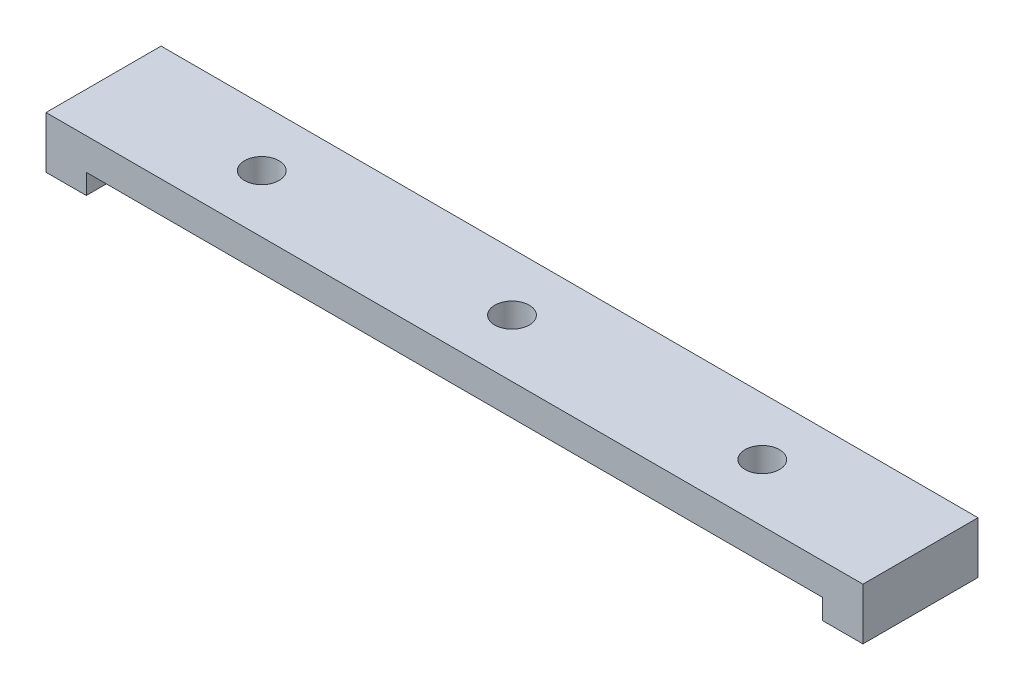
SolidWorks part; units mm, degrees
material "1060 Alloy"
ref_plane "Front Plane" through (0, 0, 0) normal (0, 0, 1) x (1, 0, 0)
ref_plane "Top Plane" through (0, 0, 0) normal (0, 1, 0) x (1, 0, 0)
ref_plane "Right Plane" through (0, 0, 0) normal (1, 0, 0) x (0, 0, -1)
sketch "Sketch1" plane through (0, 0, 0) normal (0, 1, 0) x (1, 0, 0)
  line L1 (0, 0) -> (71, 0)
  line L2 (0, 0) -> (0, 10)
  line L3 (0, 10) -> (71, 10)
  line L4 (71, 0) -> (71, 10)
  circle A0 centre (13.75, 5) radius 1.5
  circle A1 centre (35.5, 5) radius 1.5
  circle A2 centre (57.25, 5) radius 1.5
  dimension "D3" = 3
  dimension "D4" = 5
  dimension "D5" = 21.75
  dimension "D1" = 10
  dimension "D2" = 71
  dimension "D6" = 21.75
  dimension "D7" = 35.5
extrude "Boss-Extrude1" add sketch "Sketch1" along normal blind 4.5
sketch "Sketch2" plane through (0, 0, 0) normal (0, -1, 0) x (1, 0, 0)
  line L0 (0, 0) -> (71, 0) construction
  line L1 (3.5, 0) -> (67.5, 0)
  line L2 (3.5, 0) -> (3.5, -10)
  line L3 (3.5, -10) -> (67.5, -10)
  line L4 (67.5, 0) -> (67.5, -10)
  line L5 (71, -10) -> (0, -10) construction
  line L6 (0, -10) -> (0, 0) construction
  line L7 (71, 0) -> (71, -10) construction
  dimension "D1" = 3.5
  dimension "D2" = 3.5
extrude "Cut-Extrude1" cut sketch "Sketch2" against normal offset from surface (1.75 mm away) 2.75 up to face at (35.5, 4.5, -3.5)
